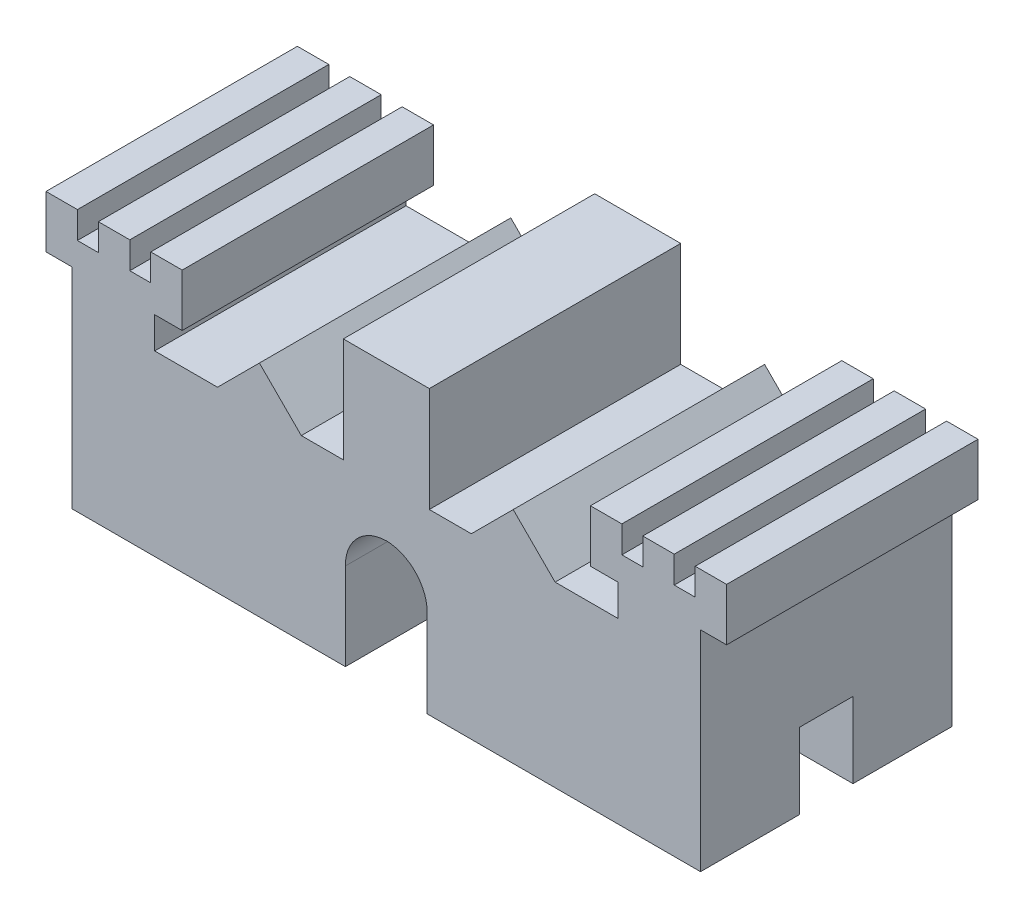
SolidWorks part; units mm, degrees
ref_plane "Front Plane" through (0, 0, 0) normal (0, 0, 1) x (1, 0, 0)
ref_plane "Top Plane" through (0, 0, 0) normal (0, 1, 0) x (1, 0, 0)
ref_plane "Right Plane" through (0, 0, 0) normal (1, 0, 0) x (0, 0, -1)
sketch "Sketch1" plane through (0, 0, 0) normal (0, 0, 1) x (1, 0, 0)
  line L0 (38.1, 0) -> (-38.1, 0)
  line L1 (-38.1, 0) -> (-38.1, 25.4)
  line L2 (-38.1, 25.4) -> (-41.2604, 25.4)
  line L3 (-41.2604, 25.4) -> (-41.2604, 31.75)
  line L4 (-41.2604, 31.75) -> (-37.4504, 31.75)
  line L5 (-37.4504, 31.75) -> (-37.4504, 28.5018)
  line L6 (-37.4504, 28.5018) -> (-34.9104, 28.5018)
  line L7 (-34.9104, 28.5018) -> (-34.9104, 31.75)
  line L8 (-34.9104, 31.75) -> (-31.1004, 31.75)
  line L9 (-31.1004, 31.75) -> (-31.1004, 28.5018)
  line L10 (-31.1004, 28.5018) -> (-28.5604, 28.5018)
  line L11 (-28.5604, 28.5018) -> (-28.5604, 31.75)
  line L12 (-28.5604, 31.75) -> (-24.7504, 31.75)
  line L13 (-24.7504, 31.75) -> (-24.7504, 25.4)
  line L14 (-24.7504, 25.4) -> (-28.0863, 25.4)
  line L15 (-28.0863, 21.59) -> (-28.0863, 25.4)
  line L16 (-28.0863, 21.59) -> (-20.4663, 21.59)
  line L17 (-20.4663, 21.59) -> (-15.3863, 26.67)
  line L18 (-15.3863, 26.67) -> (-10.3063, 21.59)
  line L19 (-10.3063, 21.59) -> (-5.2146, 21.59)
  line L20 (-5.2146, 21.59) -> (-5.2146, 34.29)
  line L21 (0, 0) -> (0, 34.29) construction
  line L22 (-5.2146, 34.29) -> (5.2146, 34.29)
  line L23 (5.2146, 21.59) -> (5.2146, 34.29)
  line L24 (10.3063, 21.59) -> (5.2146, 21.59)
  line L25 (15.3863, 26.67) -> (10.3063, 21.59)
  line L26 (20.4663, 21.59) -> (15.3863, 26.67)
  line L27 (28.0863, 21.59) -> (20.4663, 21.59)
  line L28 (28.0863, 21.59) -> (28.0863, 25.4)
  line L29 (24.7504, 25.4) -> (28.0863, 25.4)
  line L30 (24.7504, 31.75) -> (24.7504, 25.4)
  line L31 (28.5604, 31.75) -> (24.7504, 31.75)
  line L32 (28.5604, 28.5018) -> (28.5604, 31.75)
  line L33 (31.1004, 28.5018) -> (28.5604, 28.5018)
  line L34 (31.1004, 31.75) -> (31.1004, 28.5018)
  line L35 (34.9104, 31.75) -> (31.1004, 31.75)
  line L36 (34.9104, 28.5018) -> (34.9104, 31.75)
  line L37 (37.4504, 28.5018) -> (34.9104, 28.5018)
  line L38 (37.4504, 31.75) -> (37.4504, 28.5018)
  line L39 (41.2604, 31.75) -> (37.4504, 31.75)
  line L40 (41.2604, 25.4) -> (41.2604, 31.75)
  line L41 (38.1, 25.4) -> (41.2604, 25.4)
  line L42 (38.1, 0) -> (38.1, 25.4)
  dimension "D1" = 38.1
  dimension "D2" = 25.4
  dimension "D3" = 6.35
  dimension "D4" = 3.81
  dimension "D5" = 3.81
  dimension "D6" = 3.81
  dimension "D7" = 2.54
  dimension "D8" = 2.54
  dimension "D9" = 6.35
  dimension "D10" = 3.81
  dimension "D11" = 7.62
  dimension "D12" = 5.08
  dimension "D13" = 5.08
  dimension "D14" = 5.08
  dimension "D15" = 5.08
extrude "Boss-Extrude1" add sketch "Sketch1" along normal blind 30.48
sketch "Sketch2" plane through (0, 0, 30.48) normal (0, 0, 1) x (1, 0, 0)
  line L0 (0, 0) -> (0, 34.29) construction
  line L1 (4.9589, 0) -> (-4.9589, 0)
  line L2 (4.9589, 0) -> (4.9589, 10.5745)
  line L4 (-4.9589, 0) -> (-4.9589, 10.5745)
  line L5 (5.2146, 34.29) -> (-5.2146, 34.29) construction
  arc A0 (-4.9589, 10.5745) -> (0, 15.6987) centre (0.0826, 10.6572) cw
  arc A1 (4.9589, 10.5745) -> (0, 15.6987) centre (-0.0826, 10.6572) ccw
extrude "Cut-Extrude1" [suppressed] cut sketch "Sketch2" against normal blind 18.4472
sketch "Sketch4" plane through (-38.1, 0, 0) normal (-1, 0, 0) x (0, 0, 1)
  line L1 (15.24, 0) -> (15.24, 31.75) construction
  line L2 (30.48, 0) -> (0, 0) construction
  line L3 (30.48, 31.75) -> (0, 31.75) construction
  line L4 (18.4844, 0) -> (18.4844, 9.1674)
  line L5 (18.4844, 0) -> (11.9956, 0)
  line L7 (18.4844, 9.1674) -> (11.9956, 9.1674)
  line L8 (11.9956, 0) -> (11.9956, 9.1674)
  point P11 (15.24, 9.1674)
extrude "Cut-Extrude2" cut sketch "Sketch4" against normal through all
extrude "Cut-Extrude3" cut sketch "Sketch2<3>" against normal up to surface (18.4844 mm away) up to face at (0, 4.5837, 11.9956)
sketch "Sketch2<3>" plane through (0, 0, 30.48) normal (0, 0, 1) x (1, 0, 0) same geometry as "Sketch2"
